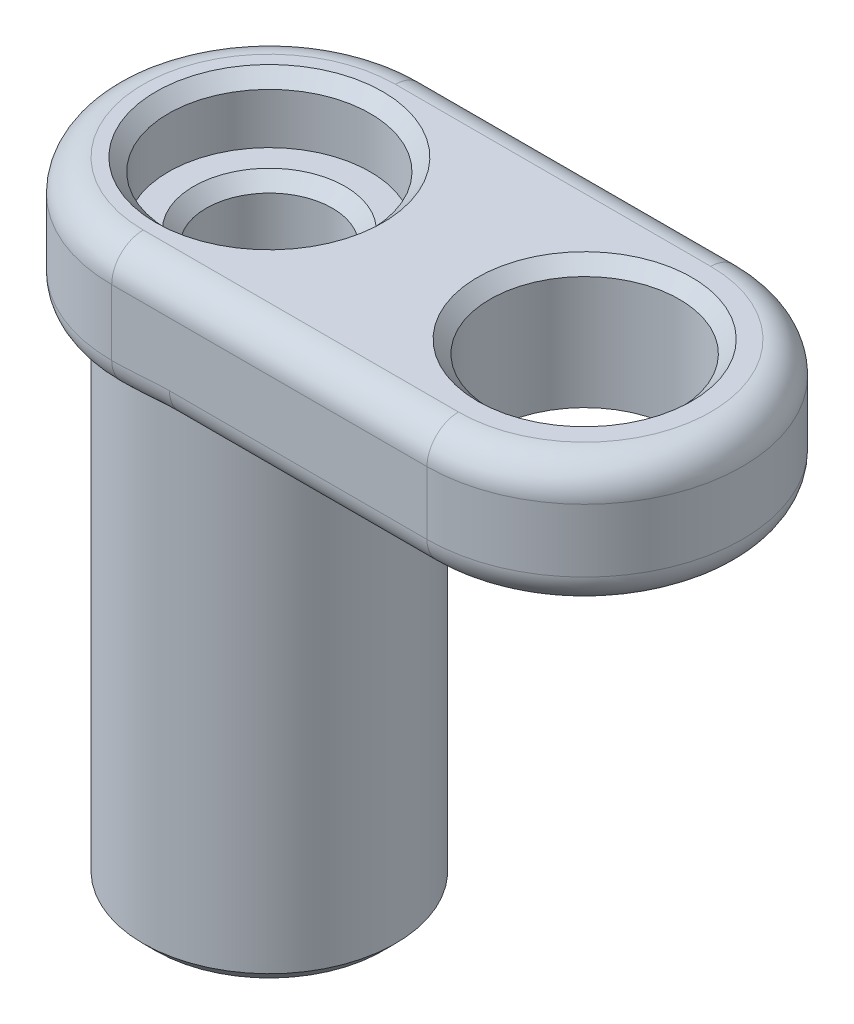
SolidWorks part; units mm, degrees
ref_plane "Front Plane" through (0, 0, 0) normal (0, 0, 1) x (1, 0, 0)
ref_plane "Top Plane" through (0, 0, 0) normal (0, 1, 0) x (1, 0, 0)
ref_plane "Right Plane" through (0, 0, 0) normal (1, 0, 0) x (0, 0, -1)
sketch "Sketch1" plane through (0, 0, 0) normal (0, 1, 0) x (1, 0, 0)
  circle A0 centre (0, 0) radius 20
  dimension "D1" = 40
extrude "Boss-Extrude1" add sketch "Sketch1" along normal blind 100
sketch "Sketch2" plane through (0, 100, 0) normal (0, 1, 0) x (1, 0, 0)
  line L0 (0, 0) -> (50, 0) construction
  line L1 (0, 25) -> (50, 25)
  line L2 (0, -25) -> (50, -25)
  arc A0 (0, 25) -> (0, -25) centre (0, 0) ccw
  arc A1 (50, -25) -> (50, 25) centre (50, 0) ccw
  point P3 (25, 0)
  dimension "D2" = 25
  dimension "D1" = 50
extrude "Boss-Extrude2" add sketch "Sketch2" against normal blind 20
hole_wizard "CBORE for M5 Hex Head Bolt1" positions "Sketch5" profile "Sketch6" counterbore size "M5" standard "ISO" end condition through all
sketch "Sketch5" plane through (0, 100, 0) normal (0, 1, 0) x (1, 0, 0)
  point P0 (0, 0)
sketch "Sketch6" plane through (0, 100, 0) normal (1, 0, 0) x (0, 0, 1)
  line L0 (0, 0) -> (0, 100)
  line L1 (0, 100) -> (10, 100)
  line L3 (10, 100) -> (10, 10)
  line L4 (10, 10) -> (16, 10)
  line L5 (16, 10) -> (16, 0)
  line L7 (16, 0) -> (0, 0)
  line L11 (0, -6.35) -> (0, 107.95) construction
  dimension "Thru Hole Dia." = 20
  dimension "Thru Hole Depth" = 100
  dimension "C'Bore Dia." = 32
  dimension "C'Bore Depth" = 10
hole_wizard "Ø1.0mm Dowel Hole1" positions "Sketch9" profile "Sketch10" hole size "Ø1.0" standard "ISO" end condition through all
sketch "Sketch9" plane through (0, 100, 0) normal (0, 1, 0) x (1, 0, 0)
  point P0 (50, 0)
sketch "Sketch10" plane through (50, 100, 0) normal (1, 0, 0) x (0, 0, 1)
  line L0 (0, 0) -> (0, 100)
  line L1 (0, 100) -> (15, 100)
  line L2 (15, 100) -> (15, 0)
  line L5 (15, 0) -> (0, 0)
  line L11 (0, -6.35) -> (0, 107.95) construction
  dimension "Thru Hole Dia." = 30
  dimension "Thru Hole Depth" = 100
chamfer "Chamfer1" distance 2 angle 45 1 edges at (0, 0, 20)
chamfer "Chamfer2" distance 2 angle 45 4 edges at (0, 90, 10) (0, 0, 10) (0, 100, 16) (50, 100, 15)
chamfer "Chamfer3" distance 2 angle 45 1 edges at (0, 80, 20)
fillet "Fillet1" radius 5 7 edges at (25, 80, -25) (75, 80, 0) (75, 100, 0) (25, 100, 25) (-25, 100, 0) (25, 80, 25) (25, 100, -25)
